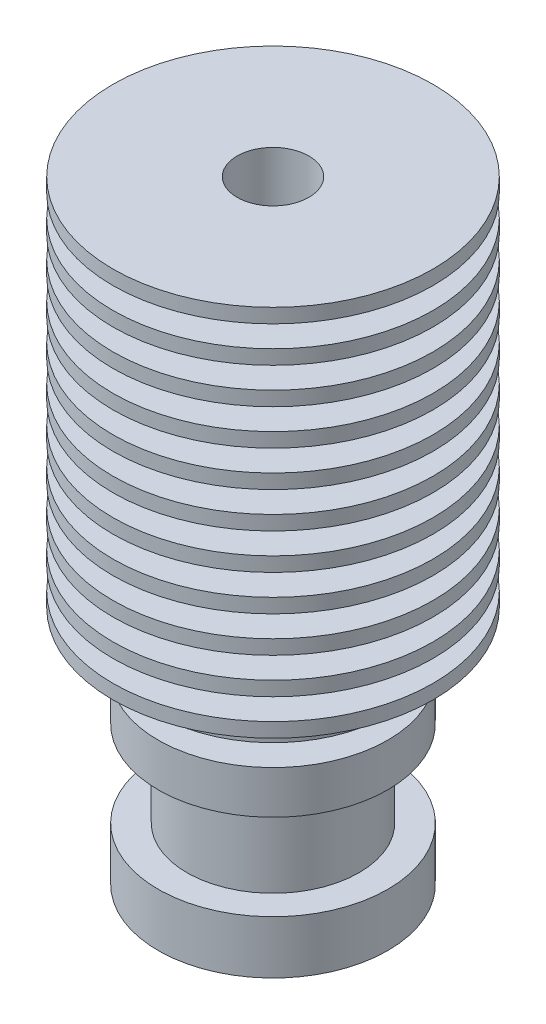
SolidWorks part; units mm, degrees
ref_plane "Спереди" through (0, 0, 0) normal (0, 0, 1) x (1, 0, 0)
ref_plane "Сверху" through (0, 0, 0) normal (0, 1, 0) x (1, 0, 0)
ref_plane "Справа" through (0, 0, 0) normal (1, 0, 0) x (0, 0, -1)
sketch "Эскиз1" plane through (0, 0, 0) normal (0, 0, 1) x (1, 0, 0)
  line L0 (5.0241, 22.7) -> (5.1027, 24.2)
  line L1 (5.1027, 24.2) -> (11.15, 24.2)
  line L2 (11.15, 24.2) -> (11.15, 25.2)
  line L3 (11.15, 25.2) -> (5.1551, 25.2)
  line L4 (5.1551, 25.2) -> (5.2337, 26.7)
  line L5 (5.2337, 26.7) -> (11.15, 26.7)
  line L6 (11.15, 26.7) -> (11.15, 27.7)
  line L7 (11.15, 27.7) -> (5.2861, 27.7)
  line L8 (5.2861, 27.7) -> (5.3647, 29.2)
  line L9 (5.3647, 29.2) -> (11.15, 29.2)
  line L10 (11.15, 29.2) -> (11.15, 30.2)
  line L11 (11.15, 30.2) -> (5.4171, 30.2)
  line L12 (5.4171, 30.2) -> (5.4957, 31.7)
  line L13 (5.4957, 31.7) -> (11.15, 31.7)
  line L14 (11.15, 31.7) -> (11.15, 32.7)
  line L15 (11.15, 32.7) -> (5.5482, 32.7)
  line L16 (5.5482, 32.7) -> (5.6268, 34.2)
  line L17 (5.6268, 34.2) -> (11.15, 34.2)
  line L18 (11.15, 34.2) -> (11.15, 35.2)
  line L19 (11.15, 35.2) -> (5.6792, 35.2)
  line L20 (5.6792, 35.2) -> (5.7578, 36.7)
  line L21 (5.7578, 36.7) -> (11.15, 36.7)
  line L22 (11.15, 36.7) -> (11.15, 37.7)
  line L23 (11.15, 37.7) -> (5.8102, 37.7)
  line L24 (5.8102, 37.7) -> (5.8888, 39.2)
  line L25 (5.8888, 39.2) -> (11.15, 39.2)
  line L26 (11.15, 39.2) -> (11.15, 40.2)
  line L27 (11.15, 40.2) -> (5.9412, 40.2)
  line L28 (5.9412, 40.2) -> (6.0198, 41.7)
  line L29 (6.0198, 41.7) -> (11.15, 41.7)
  line L30 (11.15, 41.7) -> (11.15, 42.7)
  line L31 (11.15, 42.7) -> (2.5, 42.7)
  line L32 (2.5, 42.7) -> (2.5, 24.8)
  line L33 (2.5, 24.8) -> (2.1, 24.5597)
  line L34 (2.1, 24.5597) -> (2.1, 12.7)
  line L35 (2.1, 12.7) -> (3.25, 12.7)
  line L36 (3.25, 12.7) -> (3.25, 9.7)
  line L37 (3.25, 9.7) -> (2.1, 9.7)
  line L38 (2.1, 9.7) -> (2.1, 0)
  line L39 (2.1, 0) -> (8, 0)
  line L40 (8, 0) -> (8, 3.7)
  line L41 (8, 3.7) -> (6, 3.7)
  line L42 (6, 3.7) -> (6, 9.7)
  line L43 (6, 9.7) -> (8, 9.7)
  line L44 (8, 9.7) -> (8, 12.7)
  line L45 (8, 12.7) -> (4.5, 12.7)
  line L46 (4.5, 12.7) -> (4.5786, 14.2)
  line L47 (4.5786, 14.2) -> (8, 14.2)
  line L48 (8, 14.2) -> (8, 15.2)
  line L49 (8, 15.2) -> (4.631, 15.2)
  line L50 (4.631, 15.2) -> (4.7096, 16.7)
  line L51 (4.7096, 16.7) -> (11.15, 16.7)
  line L52 (11.15, 16.7) -> (11.15, 17.7)
  line L53 (11.15, 17.7) -> (4.762, 17.7)
  line L54 (4.762, 17.7) -> (4.8407, 19.2)
  line L55 (4.8407, 19.2) -> (11.15, 19.2)
  line L56 (11.15, 19.2) -> (11.15, 20.2)
  line L57 (11.15, 20.2) -> (4.8931, 20.2)
  line L58 (4.8931, 20.2) -> (4.9717, 21.7)
  line L59 (4.9717, 21.7) -> (11.15, 21.7)
  line L60 (11.15, 21.7) -> (11.15, 22.7)
  line L61 (11.15, 22.7) -> (5.0241, 22.7)
  line L62 (0, 42.7) -> (0, 0) construction
revolve "Повернуть1" add sketch "Эскиз1" angle 360 about L62 reverse direction yes
sketch "Эскиз3" plane through (0, 0, 0) normal (0, -1, 0) x (1, 0, 0)
  line L0 (-5.2915, 6) -> (5.2915, 6) construction
  line L1 (0, 0) -> (0, 8) construction
  line L2 (-5.2915, 6) -> (5.2915, 6)
  circle A0 centre (0, 0) radius 8 construction
  arc A1 (5.2915, 6) -> (-5.2915, 6) centre (0, 0) ccw
  point P7 (0, 6)
  dimension "D1" = 2
extrude "Вырез-Вытянуть3" [suppressed] cut sketch "Эскиз3" against normal blind 13.5
